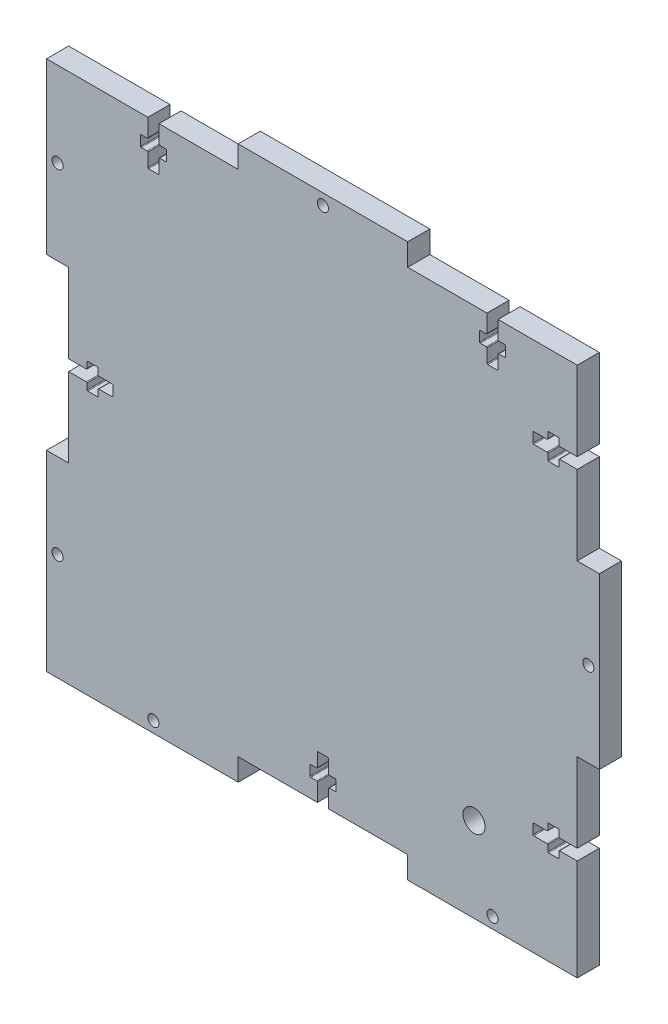
SolidWorks part; units mm, degrees
ref_plane "Front Plane" through (0, 0, 0) normal (0, 0, 1) x (1, 0, 0)
ref_plane "Top Plane" through (0, 0, 0) normal (0, 1, 0) x (1, 0, 0)
ref_plane "Right Plane" through (0, 0, 0) normal (1, 0, 0) x (0, 0, -1)
sketch "Sketch1" plane through (0, 0, 0) normal (0, 0, 1) x (1, 0, 0)
  line L0 (-69, 69) -> (-23, 69)
  line L5 (-75, -75) -> (75, -75) construction
  line L6 (-75, -75) -> (-75, 75) construction
  line L7 (-75, 75) -> (75, 75) construction
  line L8 (75, -75) -> (75, 75) construction
  line L9 (75, 23) -> (69, 23)
  line L10 (69, -23) -> (75, -23)
  line L11 (-69, -69) -> (69, -69) construction
  line L12 (-69, -69) -> (-69, 69) construction
  line L13 (-69, 69) -> (69, 69) construction
  line L14 (69, -69) -> (69, 69) construction
  line L15 (-69, -69) -> (69, 69) construction
  line L16 (69, -69) -> (69, -23)
  line L17 (-23, 69) -> (-23, 75)
  line L18 (-23, 75) -> (23, 75)
  line L19 (23, 75) -> (23, 69)
  line L20 (23, 69) -> (69, 69)
  line L21 (75, -23) -> (75, 23)
  line L22 (69, 23) -> (69, 69)
  line L23 (-75, 23) -> (-69, 23)
  line L24 (-69, 69) -> (-75, 69)
  line L25 (-75, 69) -> (-75, 23)
  line L26 (69, -69) -> (69, -75)
  line L27 (69, -75) -> (23, -75)
  line L28 (23, -75) -> (23, -69)
  line L29 (23, -69) -> (-23, -69)
  line L30 (-23, -69) -> (-23, -75)
  line L31 (-23, -75) -> (-69, -75)
  line L32 (-69, -75) -> (-69, -69) construction
  line L33 (-69, 23) -> (-69, -23)
  line L34 (-69, -23) -> (-75, -23)
  line L35 (-75, -23) -> (-75, -69)
  line L36 (-75, -69) -> (-69, -69) construction
  line L37 (-46, 69) -> (-46, -75) construction
  line L38 (-69, 69) -> (69, -69) construction
  line L39 (-75, -75) -> (-69, -75)
  line L40 (-75, -75) -> (-75, -69)
  point P0 (0, 0)
  point P6 (-7, -7)
  point P26 (0, -75)
  point P27 (-75, 0)
  dimension "D1" = 150
  dimension "D2" = 150
  dimension "D5" = 46
  dimension "D3" = 6
  dimension "D6" = 6
  dimension "D7" = 6
extrude "Box Side" add sketch "Sketch1" along normal blind 6
sketch "Sketch2" plane through (0, 0, 6) normal (0, 0, 1) x (1, 0, 0)
  line L0 (23, 72) -> (-23, 72) construction
  line L1 (23, 75) -> (23, 69) construction
  line L2 (-23, 69) -> (-23, 75) construction
  line L3 (-46, 69) -> (-46, -75) construction
  line L5 (0, 75) -> (0, 69) construction
  line L6 (-23, 75) -> (23, 75) construction
  line L7 (-69, 69) -> (69, 69) construction
  line L16 (-46, 69) -> (-46, -75) construction
  line L21 (0, -69) -> (0, 69) construction
  line L35 (-69, 69) -> (-23, 69) construction
  line L36 (-44.5, 69) -> (-44.5, 64.2)
  line L37 (-44.3, 64) -> (-42.7, 64)
  line L38 (-42.5, 63.8) -> (-42.5, 61.2)
  line L39 (-42.7, 61) -> (-44.3, 61)
  line L40 (-44.5, 60.8) -> (-44.5, 57.2)
  line L46 (-44.7, 57) -> (-47.3, 57)
  line L48 (-44.5, 69) -> (-47.5, 69)
  line L51 (-47.5, 60.8) -> (-47.5, 57.2)
  line L52 (-49.3, 61) -> (-47.7, 61)
  line L53 (-49.5, 63.8) -> (-49.5, 61.2)
  line L54 (-47.7, 64) -> (-49.3, 64)
  line L55 (-47.5, 69) -> (-47.5, 64.2)
  line L56 (47.5, 69) -> (47.5, 64.2)
  line L57 (47.7, 64) -> (49.3, 64)
  line L58 (49.5, 63.8) -> (49.5, 61.2)
  line L59 (49.3, 61) -> (47.7, 61)
  line L60 (47.5, 60.8) -> (47.5, 57.2)
  line L61 (44.5, 69) -> (47.5, 69)
  line L62 (44.7, 57) -> (47.3, 57)
  line L63 (44.5, 60.8) -> (44.5, 57.2)
  line L64 (42.7, 61) -> (44.3, 61)
  line L65 (42.5, 63.8) -> (42.5, 61.2)
  line L66 (44.3, 64) -> (42.7, 64)
  line L67 (44.5, 69) -> (44.5, 64.2)
  line L68 (-69, -69) -> (69, 69) construction
  line L69 (-69, -69) -> (69, 69) construction
  line L70 (75, 0) -> (69, 0) construction
  line L71 (72, 23) -> (72, -23) construction
  line L72 (69, 44.5) -> (64.2, 44.5)
  line L73 (64, 44.3) -> (64, 42.7)
  line L74 (63.8, 42.5) -> (61.2, 42.5)
  line L75 (61, 42.7) -> (61, 44.3)
  line L76 (60.8, 44.5) -> (57.2, 44.5)
  line L77 (57, 44.7) -> (57, 47.3)
  line L78 (69, 44.5) -> (69, 47.5)
  line L79 (60.8, 47.5) -> (57.2, 47.5)
  line L80 (61, 49.3) -> (61, 47.7)
  line L81 (63.8, 49.5) -> (61.2, 49.5)
  line L82 (64, 47.7) -> (64, 49.3)
  line L83 (69, 47.5) -> (64.2, 47.5)
  line L84 (69, -47.5) -> (64.2, -47.5)
  line L85 (64, -47.7) -> (64, -49.3)
  line L86 (63.8, -49.5) -> (61.2, -49.5)
  line L87 (61, -49.3) -> (61, -47.7)
  line L88 (60.8, -47.5) -> (57.2, -47.5)
  line L89 (69, -44.5) -> (69, -47.5)
  line L90 (57, -44.7) -> (57, -47.3)
  line L91 (60.8, -44.5) -> (57.2, -44.5)
  line L92 (61, -42.7) -> (61, -44.3)
  line L93 (63.8, -42.5) -> (61.2, -42.5)
  line L94 (64, -44.3) -> (64, -42.7)
  line L95 (69, -44.5) -> (64.2, -44.5)
  line L120 (-69, 69) -> (69, -69) construction
  line L121 (-69, 69) -> (69, -69) construction
  line L122 (-1.5, -69) -> (1.5, -69)
  line L123 (-23, -69) -> (23, -69) construction
  line L124 (1.5, -69) -> (1.5, -64.2)
  line L125 (1.7, -64) -> (3.3, -64)
  line L126 (3.5, -63.8) -> (3.5, -61.2)
  line L127 (3.3, -61) -> (1.7, -61)
  line L128 (1.5, -60.8) -> (1.5, -57.2)
  line L129 (1.3, -57) -> (-1.3, -57)
  line L130 (-1.5, -60.8) -> (-1.5, -57.2)
  line L131 (-3.3, -61) -> (-1.7, -61)
  line L132 (-3.5, -63.8) -> (-3.5, -61.2)
  line L133 (-1.7, -64) -> (-3.3, -64)
  line L134 (-1.5, -69) -> (-1.5, -64.2)
  line L135 (-69, -1.5) -> (-64.2, -1.5)
  line L136 (-64, -1.7) -> (-64, -3.3)
  line L137 (-63.8, -3.5) -> (-61.2, -3.5)
  line L138 (-61, -3.3) -> (-61, -1.7)
  line L139 (-60.8, -1.5) -> (-57.2, -1.5)
  line L140 (-57, 1.3) -> (-57, -1.3)
  line L141 (-60.8, 1.5) -> (-57.2, 1.5)
  line L142 (-61, 3.3) -> (-61, 1.7)
  line L143 (-63.8, 3.5) -> (-61.2, 3.5)
  line L144 (-64, 1.7) -> (-64, 3.3)
  line L145 (-69, 1.5) -> (-64.2, 1.5)
  line L146 (-69, -1.5) -> (-69, 1.5)
  line L147 (-69, -72) -> (-23, -72) construction
  line L148 (-23, 69) -> (-75, 69) construction
  line L149 (-23, -75) -> (-23, -69) construction
  line L150 (-69, -69) -> (-69, -75) construction
  line L151 (-75, -75) -> (-23, -75) construction
  circle A0 centre (0, 72) radius 1.5
  arc A1 (-44.5, 57.2) -> (-44.7, 57) centre (-44.7, 57.2) cw
  arc A2 (-44.3, 61) -> (-44.5, 60.8) centre (-44.3, 60.8) ccw
  arc A3 (-42.5, 61.2) -> (-42.7, 61) centre (-42.7, 61.2) cw
  arc A4 (-42.7, 64) -> (-42.5, 63.8) centre (-42.7, 63.8) cw
  arc A5 (-44.5, 64.2) -> (-44.3, 64) centre (-44.3, 64.2) ccw
  arc A6 (-47.5, 64.2) -> (-47.7, 64) centre (-47.7, 64.2) cw
  arc A7 (-49.3, 64) -> (-49.5, 63.8) centre (-49.3, 63.8) ccw
  arc A8 (-49.5, 61.2) -> (-49.3, 61) centre (-49.3, 61.2) ccw
  arc A9 (-47.7, 61) -> (-47.5, 60.8) centre (-47.7, 60.8) cw
  arc A10 (-47.5, 57.2) -> (-47.3, 57) centre (-47.3, 57.2) ccw
  arc A11 (47.5, 57.2) -> (47.3, 57) centre (47.3, 57.2) cw
  arc A12 (47.7, 61) -> (47.5, 60.8) centre (47.7, 60.8) ccw
  arc A13 (49.5, 61.2) -> (49.3, 61) centre (49.3, 61.2) cw
  arc A14 (49.3, 64) -> (49.5, 63.8) centre (49.3, 63.8) cw
  arc A15 (47.5, 64.2) -> (47.7, 64) centre (47.7, 64.2) ccw
  arc A16 (44.5, 64.2) -> (44.3, 64) centre (44.3, 64.2) cw
  arc A17 (42.7, 64) -> (42.5, 63.8) centre (42.7, 63.8) ccw
  arc A18 (42.5, 61.2) -> (42.7, 61) centre (42.7, 61.2) ccw
  arc A19 (44.3, 61) -> (44.5, 60.8) centre (44.3, 60.8) cw
  arc A20 (44.5, 57.2) -> (44.7, 57) centre (44.7, 57.2) ccw
  arc A21 (57.2, 44.5) -> (57, 44.7) centre (57.2, 44.7) cw
  arc A22 (61, 44.3) -> (60.8, 44.5) centre (60.8, 44.3) ccw
  arc A23 (61.2, 42.5) -> (61, 42.7) centre (61.2, 42.7) cw
  arc A24 (64, 42.7) -> (63.8, 42.5) centre (63.8, 42.7) cw
  arc A25 (64.2, 44.5) -> (64, 44.3) centre (64.2, 44.3) ccw
  arc A26 (64.2, 47.5) -> (64, 47.7) centre (64.2, 47.7) cw
  arc A27 (64, 49.3) -> (63.8, 49.5) centre (63.8, 49.3) ccw
  arc A28 (61.2, 49.5) -> (61, 49.3) centre (61.2, 49.3) ccw
  arc A29 (61, 47.7) -> (60.8, 47.5) centre (60.8, 47.7) cw
  arc A30 (57.2, 47.5) -> (57, 47.3) centre (57.2, 47.3) ccw
  arc A31 (57.2, -47.5) -> (57, -47.3) centre (57.2, -47.3) cw
  arc A32 (61, -47.7) -> (60.8, -47.5) centre (60.8, -47.7) ccw
  arc A33 (61.2, -49.5) -> (61, -49.3) centre (61.2, -49.3) cw
  arc A34 (64, -49.3) -> (63.8, -49.5) centre (63.8, -49.3) cw
  arc A35 (64.2, -47.5) -> (64, -47.7) centre (64.2, -47.7) ccw
  arc A36 (64.2, -44.5) -> (64, -44.3) centre (64.2, -44.3) cw
  arc A37 (64, -42.7) -> (63.8, -42.5) centre (63.8, -42.7) ccw
  arc A38 (61.2, -42.5) -> (61, -42.7) centre (61.2, -42.7) ccw
  arc A39 (61, -44.3) -> (60.8, -44.5) centre (60.8, -44.3) cw
  arc A40 (57.2, -44.5) -> (57, -44.7) centre (57.2, -44.7) ccw
  circle A41 centre (72, 0) radius 1.5
  arc A62 (1.5, -57.2) -> (1.3, -57) centre (1.3, -57.2) ccw
  arc A63 (1.7, -61) -> (1.5, -60.8) centre (1.7, -60.8) cw
  arc A64 (3.5, -61.2) -> (3.3, -61) centre (3.3, -61.2) ccw
  arc A65 (3.3, -64) -> (3.5, -63.8) centre (3.3, -63.8) ccw
  arc A66 (1.5, -64.2) -> (1.7, -64) centre (1.7, -64.2) cw
  arc A67 (-1.5, -64.2) -> (-1.7, -64) centre (-1.7, -64.2) ccw
  arc A68 (-3.3, -64) -> (-3.5, -63.8) centre (-3.3, -63.8) cw
  arc A69 (-3.5, -61.2) -> (-3.3, -61) centre (-3.3, -61.2) cw
  arc A70 (-1.7, -61) -> (-1.5, -60.8) centre (-1.7, -60.8) ccw
  arc A71 (-1.5, -57.2) -> (-1.3, -57) centre (-1.3, -57.2) cw
  arc A72 (-57.2, -1.5) -> (-57, -1.3) centre (-57.2, -1.3) ccw
  arc A73 (-61, -1.7) -> (-60.8, -1.5) centre (-60.8, -1.7) cw
  arc A74 (-61.2, -3.5) -> (-61, -3.3) centre (-61.2, -3.3) ccw
  arc A75 (-64, -3.3) -> (-63.8, -3.5) centre (-63.8, -3.3) ccw
  arc A76 (-64.2, -1.5) -> (-64, -1.7) centre (-64.2, -1.7) cw
  arc A77 (-64.2, 1.5) -> (-64, 1.7) centre (-64.2, 1.7) ccw
  arc A78 (-64, 3.3) -> (-63.8, 3.5) centre (-63.8, 3.3) cw
  arc A79 (-61.2, 3.5) -> (-61, 3.3) centre (-61.2, 3.3) cw
  arc A80 (-61, 1.7) -> (-60.8, 1.5) centre (-60.8, 1.7) ccw
  arc A81 (-57.2, 1.5) -> (-57, 1.3) centre (-57.2, 1.3) cw
  circle A82 centre (-46, -72) radius 1.5
  circle A83 centre (46, -72) radius 1.5
  circle A84 centre (-72, 46) radius 1.5
  circle A85 centre (-72, -46) radius 1.5
  point P6 (0, 72)
  point P38 (0, 0)
  point P56 (-46, 57)
  point P88 (46, 57)
  point P161 (57, 46)
  point P162 (57, -46)
  point P198 (0, -57)
  point P231 (-57, 0)
  point P234 (-42.5, 62.5)
  dimension "D1" = 3
  dimension "D2" = 0.2
  dimension "D8" = 0.2
  dimension "D14" = 3
  dimension "D4" = 3
  dimension "D7" = 1.5
  dimension "D10" = 3
  dimension "D12" = 1.5
  dimension "D9" = 12
  dimension "D11" = 5
  dimension "D13" = 7
  dimension "D3" = 12
  dimension "D5" = 7
  dimension "D6" = 5
extrude "Screw Cut-outs" cut sketch "Sketch2" against normal through all
sketch "Sketch3" plane through (0, 0, 6) normal (0, 0, 1) x (1, 0, 0)
  line L4 (41, -49) -> (50041, -49) construction
  line L5 (41.5774, -55) -> (50041.5774, -55) construction
  line L7 (1.5, -69) -> (23, -69) construction
  line L8 (44, -52) -> (44, -50052) construction
  line L9 (69, -75) -> (69, -47.5) construction
  circle A0 centre (41, -52) radius 3
  dimension "D2" = 6
  dimension "D1" = 14
  dimension "D3" = 25
extrude "Cut-Extrude1" cut sketch "Sketch3" against normal through all
equation "\"filletRadius\"=0.2"
equation "\"D8@Sketch2\"=\"filletRadius\""
equation "\"D2@Sketch2\"=\"filletRadius\""
equation "\"fingerWidth\"= 46"
equation "\"D5@Sketch1\"=\"fingerWidth\""
equation "\"wallThickness\"= 6"
equation "\"D3@Sketch1\" = \"wallThickness\""
equation "\"D6@Sketch1\" = \"wallThickness\""
equation "\"D7@Sketch1\" = \"wallThickness\""
equation "\"D1@Box Side\" = \"wallThickness\""
equation "\"M3\"= 3"
equation "\"D14@Sketch2\"=\"M3\""
equation "\"D1@Sketch2\"=\"M3\""
equation "\"D12@Sketch2\"=\"M3\"/2"
equation "\"nutThickness\"=3"
equation "\"D10@Sketch2\" = \"nutThickness\""
equation "\"boltLength\"= 12"
equation "\"D9@Sketch2\" = \"boltLength\""
equation "\"distanceToNut\"= 5"
equation "\"D11@Sketch2\" = \"distanceToNut\""
equation "\"D13@Sketch2\" = \"nutWidth\""
equation "\"D7@Sketch2\"=\"M3\"/2"
equation "\"D4@Sketch2\" = \"nutThickness\""
equation "\"D3@Sketch2\" = \"boltLength\""
equation "\"D5@Sketch2\" = \"nutWidth\""
equation "\"D6@Sketch2\" = \"distanceToNut\""
equation "\"sideLength\"=150"
equation "\"D1@Sketch1\"=\"sideLength\""
equation "\"D2@Sketch1\"=\"sideLength\""
equation "\"nutWidth\"=7"
